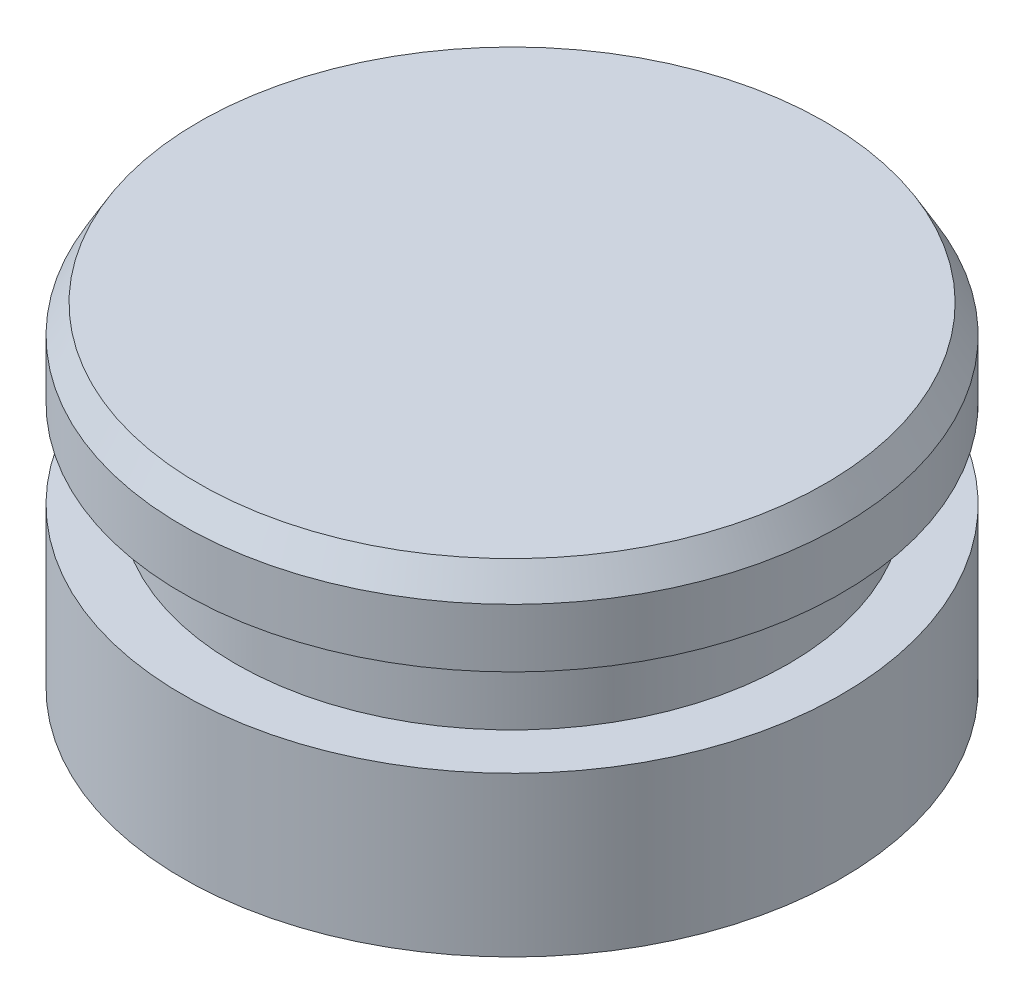
SolidWorks part; units mm, degrees
ref_plane "Front Plane" through (0, 0, 0) normal (0, 0, 1) x (1, 0, 0)
ref_plane "Top Plane" through (0, 0, 0) normal (0, 1, 0) x (1, 0, 0)
ref_plane "Right Plane" through (0, 0, 0) normal (1, 0, 0) x (0, 0, -1)
sketch "Sketch1" plane through (0, 0, 0) normal (0, 0, 1) x (1, 0, 0)
  line L0 (0, 0) -> (0, 9.652) construction
  line L1 (0, 0) -> (-9.5377, 0)
  line L4 (-8.001, 4.6037) -> (-8.001, 7.1437)
  line L5 (-8.001, 7.1437) -> (-9.5377, 7.1437)
  line L6 (-9.5377, 7.1437) -> (-9.5377, 9.652)
  line L7 (-9.5377, 9.652) -> (0, 9.652)
  line L9 (0, 0) -> (0, 9.652)
  line L11 (-8.001, 4.6037) -> (-9.5377, 4.6037)
  line L12 (-9.5377, 4.6037) -> (-9.5377, 0)
  point P5 (0, 0)
  dimension "D1" = 9.652
  dimension "D2" = 9.5377
  dimension "D3" = 2.54
  dimension "D6" = 8.001
  dimension "D7" = 7.1437
revolve "Revolve1" add sketch "Sketch1" angle 360 about L9
chamfer "Chamfer1" distance 0.4704 angle 60 1 edges at (0, 9.652, -9.5377) first distance on face at (0, 9.652, -9.5377)
